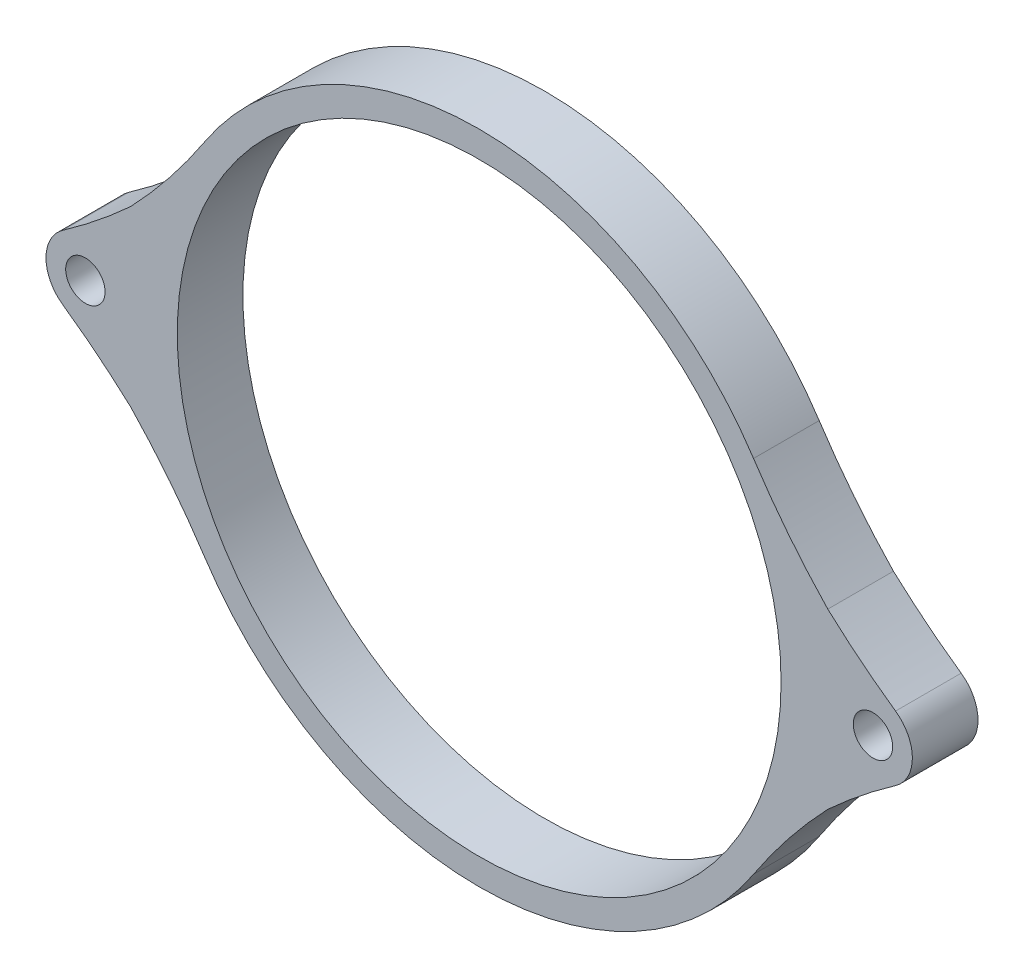
SolidWorks part; units mm, degrees
ref_plane "Front" through (0, 0, 0) normal (0, 0, 1) x (1, 0, 0)
ref_plane "Top" through (0, 0, 0) normal (0, 1, 0) x (1, 0, 0)
ref_plane "Right" through (0, 0, 0) normal (1, 0, 0) x (0, 0, -1)
sketch "Esquisse1" plane through (0, 0, 0) normal (0, 0, 1) x (1, 0, 0)
  line L0 (-30, 3) -> (-22.5479, 10.7977)
  line L7 (-30, -3) -> (-22.5479, -10.7977)
  line L8 (30, 3) -> (22.5479, 10.7977)
  line L9 (30, -3) -> (22.5479, -10.7977)
  circle A0 centre (0, 0) radius 25
  circle A1 centre (0, 0) radius 23
  circle A2 centre (30, 0) radius 1.5
  circle A3 centre (-30, 0) radius 1.5
  circle A4 centre (-30, 0) radius 3
  circle A5 centre (30, 0) radius 3
  point P18 (0, 0)
  dimension "D1" = 50
  dimension "D2" = 46
  dimension "D3" = 3
  dimension "D4" = 3
  dimension "D5" = 6
  dimension "D6" = 6
  dimension "D7" = 30
  dimension "D8" = 30
extrude "Boss.-Extru.1" add sketch "Esquisse1" along normal blind 5 contours A0 A1 | A5 L8 A0 L9 | A5 A2 | A4 A3 | A4 L7 A0 L0 region at (-26.1024, 0, 0) region at (-27.9387, 2.0613, 0) region at (0, 24.2929, 0) region at (26.1024, 0, 0) region at (32.0613, 2.0613, 0)
fillet "Congé1" radius 50 4 edges at (22.5479, -10.7977, 2.5) (-22.5479, -10.7977, 2.5) (-22.5479, 10.7977, 2.5) (22.5479, 10.7977, 2.5)
fillet "Congé2" radius 50 4 edges at (-30, 3, 2.5) (-30, -3, 2.5) (30, -3, 2.5) (30, 3, 2.5)
